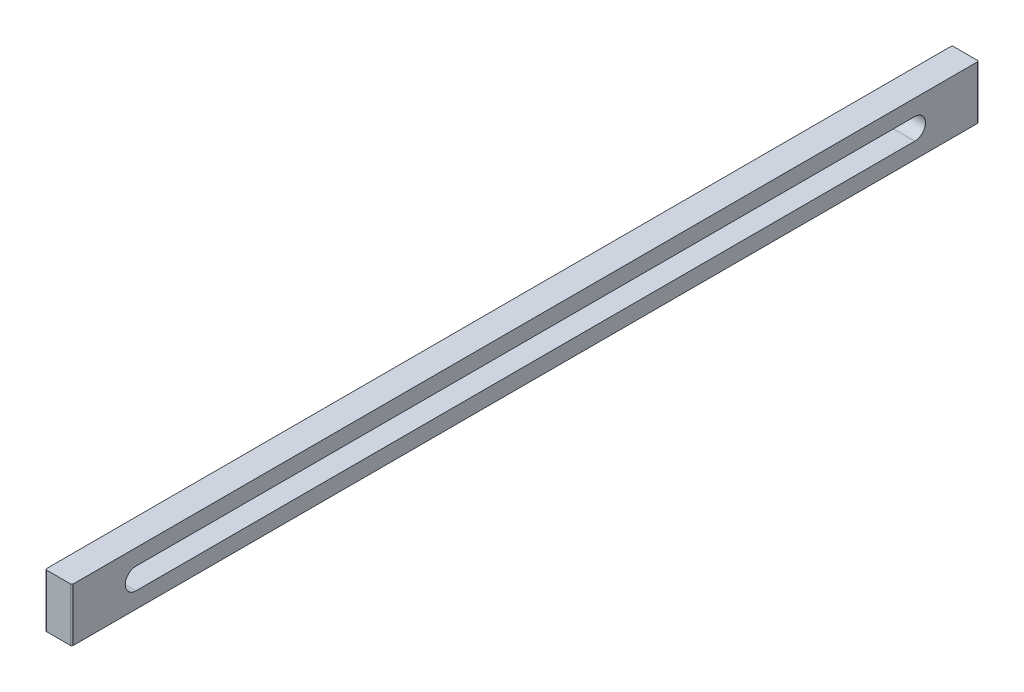
SolidWorks part; units mm, degrees
ref_plane "Front Plane" through (0, 0, 0) normal (0, 0, 1) x (1, 0, 0)
ref_plane "Top Plane" through (0, 0, 0) normal (0, 1, 0) x (1, 0, 0)
ref_plane "Right Plane" through (0, 0, 0) normal (1, 0, 0) x (0, 0, -1)
sketch "Sketch1" plane through (0, 0, 0) normal (0, 1, 0) x (1, 0, 0)
  line L0 (11.1524, 3.8525) -> (11.1524, 173.3525)
  line L1 (16.1524, 3.8525) -> (16.1524, 173.3525)
  line L2 (11.4024, 3.6025) -> (15.9024, 3.6025)
  line L3 (11.4024, 173.6025) -> (15.9024, 173.6025)
  line L4 (16.1524, 3.6025) -> (16.1524, 173.6025) construction
  line L5 (11.1524, 3.6025) -> (11.1524, 173.6025) construction
  arc A0 (15.9024, 3.6025) -> (16.1524, 3.8525) centre (15.9024, 3.8525) ccw
  arc A1 (11.4024, 3.6025) -> (11.1524, 3.8525) centre (11.4024, 3.8525) cw
  arc A2 (16.1524, 173.3525) -> (15.9024, 173.6025) centre (15.9024, 173.3525) ccw
  arc A3 (11.4024, 173.6025) -> (11.1524, 173.3525) centre (11.4024, 173.3525) ccw
  dimension "D2" = 0.25
  dimension "D1" = 5
extrude "Boss-Extrude1" add sketch "Sketch1" along normal blind 10
sketch "Sketch2" plane through (16.1524, 0, 0) normal (1, 0, 0) x (0, 0, -1)
  line L4 (15.6025, 5) -> (161.6025, 5) construction
  line L5 (15.6025, 7) -> (161.6025, 7)
  line L6 (15.6025, 3) -> (161.6025, 3)
  arc A0 (15.6025, 7) -> (15.6025, 3) centre (15.6025, 5) ccw
  arc A1 (161.6025, 3) -> (161.6025, 7) centre (161.6025, 5) ccw
  point P8 (88.6025, 5)
extrude "Cut-Extrude1" cut sketch "Sketch2" against normal blind 10
